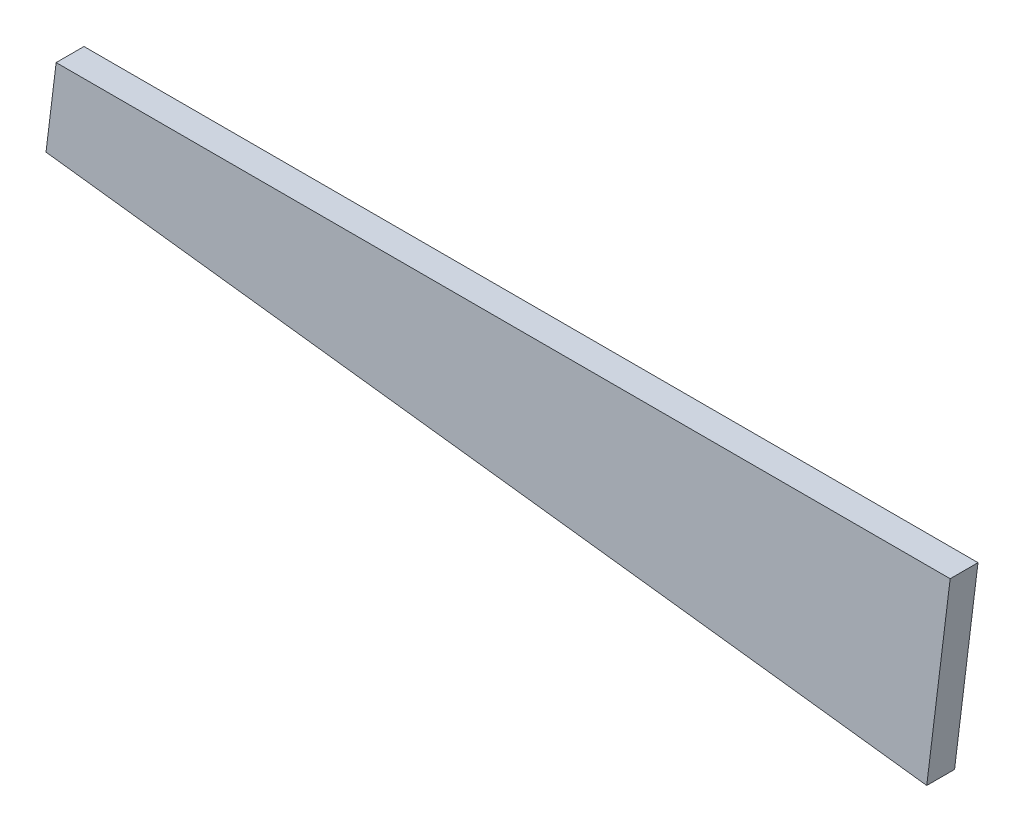
SolidWorks part; units mm, degrees
ref_plane "Front Plane" through (0, 0, 0) normal (0, 0, 1) x (1, 0, 0)
ref_plane "Top Plane" through (0, 0, 0) normal (0, 1, 0) x (1, 0, 0)
ref_plane "Right Plane" through (0, 0, 0) normal (1, 0, 0) x (0, 0, -1)
sketch "Sketch1" plane through (0, 0, 0) normal (0, 0, 1) x (1, 0, 0)
  line L0 (-195.3168, -62.6592) -> (-182.6168, -62.6592)
  line L4 (-182.6168, -62.6592) -> (-182.6168, -69.0092)
  line L5 (-182.6168, -69.0092) -> (-112.7668, -69.0092)
  line L6 (-112.7668, -69.0092) -> (-112.7668, -62.6592)
  line L7 (-112.7668, -62.6592) -> (-74.6668, -62.6592)
  line L8 (-74.6668, -62.6592) -> (-74.6668, -69.0092)
  line L9 (-74.6668, -69.0092) -> (7.8832, -69.0092)
  line L10 (7.8832, -69.0092) -> (2.5379, -112.5435)
  line L11 (2.5379, -112.5435) -> (-198.4122, -87.8699)
  line L12 (-198.4122, -87.8699) -> (-195.3168, -62.6592)
  line L13 (-1124.7791, 73.1794) -> (-1105.8711, 70.8577) construction
  dimension "D1" = 12.7
  dimension "D2" = 6.35
  dimension "D3" = 69.85
  dimension "D4" = 38.1
  dimension "D5" = 82.55
  dimension "D6" = 25.4
extrude "Boss-Extrude1" add sketch "Sketch1" against normal blind 6.35
sketch "Sketch2" plane through (0, 0, 0) normal (0, 0, 1) x (1, 0, 0)
  line L0 (-195.3168, -62.6592) -> (-74.6668, -62.6592)
  line L1 (-74.6668, -62.6592) -> (-74.6668, -69.0092)
  line L2 (-74.6668, -69.0092) -> (-196.0964, -69.0092)
  line L3 (-195.3168, -62.6592) -> (-198.4122, -87.8699) construction
  line L4 (-196.0964, -69.0092) -> (-195.3168, -62.6592)
extrude "Cut-Extrude1" cut sketch "Sketch2" against normal through all
